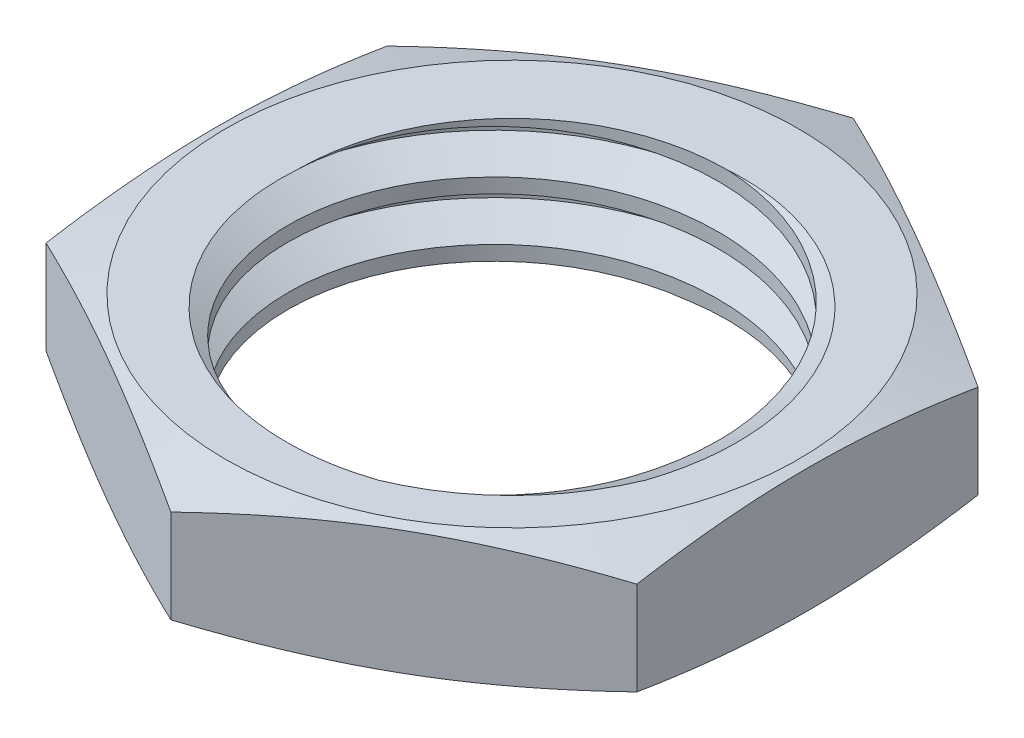
SolidWorks part; units mm, degrees
ref_plane "Front Plane" through (0, 0, 0) normal (0, 0, 1) x (1, 0, 0)
ref_plane "Top Plane" through (0, 0, 0) normal (0, 1, 0) x (1, 0, 0)
ref_plane "Right Plane" through (0, 0, 0) normal (1, 0, 0) x (0, 0, -1)
sketch "Sketch1" plane through (0, 0, 0) normal (0, 1, 0) x (1, 0, 0)
  line L1 (0, -4.6765) -> (4.05, -2.3383)
  line L2 (4.05, -2.3383) -> (4.05, 2.3383)
  line L3 (4.05, 2.3383) -> (0, 4.6765)
  line L4 (0, 4.6765) -> (-4.05, 2.3383)
  line L5 (-4.05, 2.3383) -> (-4.05, -2.3383)
  line L6 (-4.05, -2.3383) -> (0, -4.6765)
  circle A0 centre (0, 0) radius 4.05 construction
  circle A1 centre (0, 0) radius 2.95
  dimension "D2" = 5.9
  dimension "D1" = 8.1
extrude "Boss-Extrude1" add sketch "Sketch1" along normal blind 1.78
ref_axis "Axis1" through (0, 1.78, 0) along (0, -1, 0)
ref_plane "Plane1" through (0, 0, 0) normal (0.5, 0, -0.866) x (-0.866, 0, -0.5)
sketch "Sketch2" plane through (0, 0, 0) normal (0.5, 0, -0.866) x (-0.866, 0, -0.5)
  line L0 (-4.6765, 1.53) -> (-3.9265, 1.78)
  line L1 (-4.6765, 1.78) -> (-4.6765, 0) construction
  line L2 (-2.3383, 1.78) -> (-4.6765, 1.78) construction
  line L3 (-3.9265, 1.78) -> (-4.6765, 1.78)
  line L4 (-4.6765, 1.78) -> (-4.6765, 1.53)
  line L5 (2.3383, 0.89) -> (-4.6765, 0.89) construction
  line L6 (2.3383, 1.78) -> (2.3383, 0) construction
  line L7 (-4.6765, 0.25) -> (-3.9265, 0)
  line L8 (-3.9265, 0) -> (-4.6765, 0)
  line L9 (-4.6765, 0) -> (-4.6765, 0.25)
  dimension "D1" = 0.75
  dimension "D2" = 0.25
revolve "Cut-Revolve2" cut sketch "Sketch2" angle 360 about axis through (0, 1.78, 0) along (0, -1, 0)
thread "Thread1" pitch 0.8 method cut profile "Thread Profile1" start angle 0, offset 0.8, length 0, pitch 0.8, diameter 5.9
ref_plane "Plane2" through (-2.95, 2.58, 0) normal (0, 0, 1) x (-1, 0, 0)
sketch "Thread Profile1" plane through (-2.95, 2.58, 0) normal (0, 0, 1) x (-1, 0, 0)
  line L0 (0, 0) -> (0, 0.8) construction
  line L1 (0, 0) -> (0.433, 0.25)
  line L2 (0.433, 0.25) -> (0.433, 0.35)
  line L3 (0.433, 0.35) -> (0, 0.6)
  line L4 (0.433, 0.3) -> (0, 0.3) construction
  line L11 (0, 0) -> (0, 0.6)
  point P2 (0, 0)
  dimension "Pitch" = 0.8
  dimension "Profile_Angle" = 60
  dimension "Profile_Land" = 0.1
  dimension "Profile_Height" = 0.433
